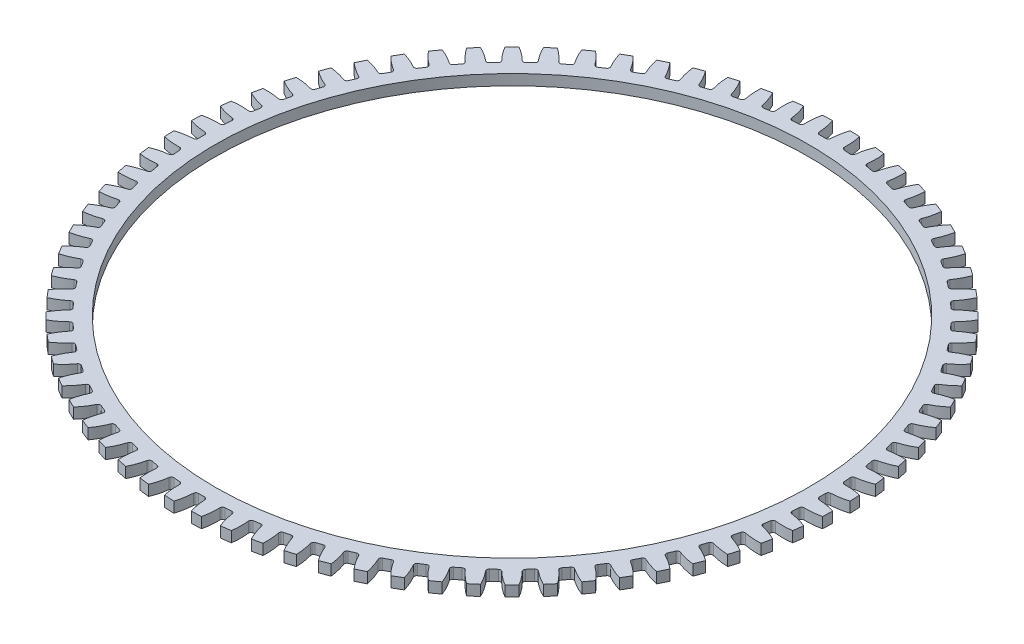
SolidWorks part; units mm, degrees
ref_plane "Front Plane" through (0, 0, 0) normal (0, 0, 1) x (1, 0, 0)
ref_plane "Top Plane" through (0, 0, 0) normal (0, 1, 0) x (1, 0, 0)
ref_plane "Right Plane" through (0, 0, 0) normal (1, 0, 0) x (0, 0, -1)
sketch "Sketch1" plane through (0, 0, 0) normal (0, 1, 0) x (1, 0, 0)
  circle A0 centre (0, 0) radius 383.8
  circle A1 centre (0, 0) radius 367.5 construction
  circle A2 centre (0, 0) radius 367.5 construction
  circle A3 centre (0, 0) radius 393.9
  circle A4 centre (0, 0) radius 371.175
  dimension "D2" = 767.6
  dimension "D3" = 787.8
  dimension "D1" = 16.3
  dimension "D4" = 22.725
extrude "Boss-Extrude1" add sketch "Sketch1" along normal mid plane 12.7 contours A3
sketch "Sketch4" plane through (0, 0, 0) normal (0, 1, 0) x (1, 0, 0)
  line L0 (0, 0) -> (0, 393.9) construction
  line L1 (-7.932, 383.718) -> (7.932, 383.718) construction
  line L2 (0, 0) -> (-6.7143, 371.1143) construction
  line L3 (0, 338.7337) -> (-11.4619, 403.7373) construction
  line L4 (0, 0) -> (16.2779, 393.5635) construction
  line L5 (7.932, 383.718) -> (23.7823, 383.0625) construction
  circle A0 centre (0, 0) radius 393.9 construction
  arc A1 (-14.1811, 403.651) -> (-6.7143, 371.1143) centre (-87.7235, 369.6486) cw
  arc A2 (14.1811, 403.651) -> (6.7143, 371.1143) centre (87.7235, 369.6486) ccw
  circle A3 centre (0, 0) radius 371.175 construction
  arc A4 (6.7143, 371.1143) -> (-6.7143, 371.1143) centre (0, 0) ccw
  circle A6 centre (0, 0) radius 383.8 construction
  circle A7 centre (0, 0) radius 403.9
  arc A8 (14.1811, 403.651) -> (-14.1811, 403.651) centre (0, 0) ccw
  dimension "D3" = 2.368
  dimension "D2" = 10
  dimension "D1" = 10
extrude "Cut-Extrude3" cut sketch "Sketch4" against normal through all both and the other way through all
fillet "Fillet1" radius 3.03 2 edges at (6.7143, 0, -371.1143) (-6.7143, 0, -371.1143)
pattern_circular "CirPattern2" count 76 over 360 about axis through (0, 6.35, 0) along (0, -1, 0) of "Cut-Extrude3", "Fillet1"
sketch "Sketch3" plane through (0, 0, 0) normal (0, 1, 0) x (1, 0, 0)
  circle A0 centre (0, 0) radius 354.8
  circle A1 centre (0, 0) radius 367.5 construction
  dimension "D1" = 12.7
extrude "Cut-Extrude2" cut sketch "Sketch3" along normal through all both and the other way through all contours A0 region at (0, 0, 0)
ref_axis "Centerline Axis" through (0, 0, 0) along (0, 1, 0)
equation "\"Module\"= 10.1mm"
equation "\"Number of Teeth\"= 76"
equation "\"D2@Sketch1\"=\"Module\"*\"Number of Teeth\""
equation "\"D3@Sketch1\"=(\"Number of Teeth\"+ 2) * \"Module\""
equation "\"Distance From Teeth Centerline to Cut Centerline\"= 180 / \"Number of Teeth\""
equation "\"D3@Sketch4\"=\"Distance From Teeth Centerline to Cut Centerline\""
equation "\"D1@Fillet1\"=.3* \"Module\""
equation "\"D1@CirPattern2\"=\"Number of Teeth\""
equation "\"D4@Sketch1\"=\"Module\" * (if( \"Module\" => 1.25, 2.25, 2.4)) "
